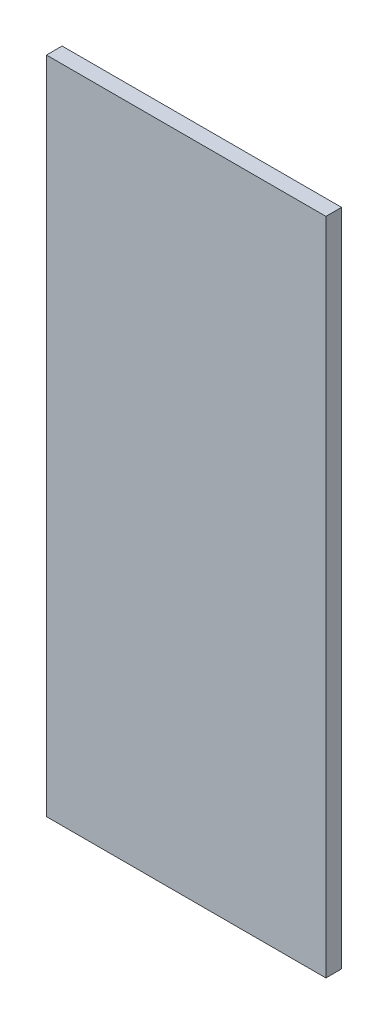
SolidWorks part; units mm, degrees
material "Perspex (TM) GS Acrylic Cast Sheet"
ref_plane "Front Plane" through (0, 0, 0) normal (0, 0, 1) x (1, 0, 0)
ref_plane "Top Plane" through (0, 0, 0) normal (0, 1, 0) x (1, 0, 0)
ref_plane "Right Plane" through (0, 0, 0) normal (1, 0, 0) x (0, 0, -1)
sketch "Sketch1" plane through (0, 0, 0) normal (0, 0, 1) x (1, 0, 0)
  line L1 (-80.5, -190) -> (80.5, -190)
  line L2 (-80.5, -190) -> (-80.5, 190)
  line L3 (-80.5, 190) -> (80.5, 190)
  line L4 (80.5, -190) -> (80.5, 190)
  line L5 (-80.5, -190) -> (80.5, 190) construction
  line L6 (-80.5, 190) -> (80.5, -190) construction
  point P0 (0, 0)
  dimension "D1" = 161
  dimension "D2" = 380
extrude "Boss-Extrude1" add sketch "Sketch1" along normal blind 9
sketch "Sketch2" plane through (0, 0, 9) normal (0, 0, 1) x (1, 0, 0)
  line L0 (6, -130) -> (6, -190) construction
  line L2 (-80.5, -190) -> (80.5, -190) construction
  line L3 (-6, -190) -> (-6, -150) construction
  circle A0 centre (6, -130) radius 5.5
  circle A1 centre (-6, -150) radius 5.5
  point P7 (0, -190)
  dimension "D1" = 11
  dimension "D2" = 60
  dimension "D3" = 6
  dimension "D4" = 6
  dimension "D5" = 40
extrude "Cut-Extrude1" [suppressed] cut sketch "Sketch2" against normal through all
equation "\"PCLength\"= 143mm'Length across I/O from PS to GPU"
equation "\"PCWidth\"= 340mm'Distance of longest part parallel to GPU(ussually GPU)"
equation "\"PCHeight\"= 190mm'Tallest point with mobo laying flat"
equation "\"WallThickness\"= 9mm'Thickness of each outer tank wall"
equation "\"ThermoBarrierThickness\"= 6mm'Thickness of barrier between hot side and cold side"
equation "\"HotSideGap\"= 15mm'Space in the hot side that hot fluid flows into"
equation "\"PCClearance\"= 40mm'Clearance from top of tank to top of PC"
equation "\"RadiatorHeight\"= 277.37mm'Final Height from ground of radiators"
equation "\"D1@Sketch1\"=\"PCLength\" + (2 * \"WallThickness\")"
equation "\"D2@Sketch1\"=\"PCWidth\" + \"PCClearance\""
equation "\"D1@Boss-Extrude1\"=\"WallThickness\""
